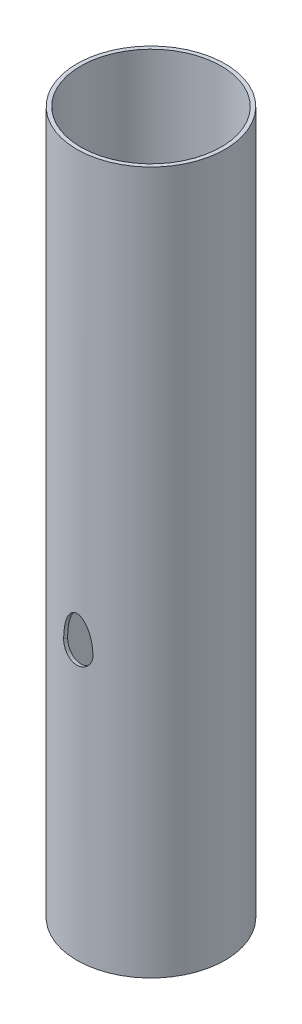
SolidWorks part; units mm, degrees
ref_plane "Front Plane" through (0, 0, 0) normal (0, 0, 1) x (1, 0, 0)
ref_plane "Top Plane" through (0, 0, 0) normal (0, 1, 0) x (1, 0, 0)
ref_plane "Right Plane" through (0, 0, 0) normal (1, 0, 0) x (0, 0, -1)
sketch "Sketch2" plane through (0, 0, 0) normal (0, 1, 0) x (1, 0, 0)
  circle A0 centre (0, 0) radius 36
  circle A1 centre (0, 0) radius 38
  dimension "D1" = 2
  dimension "D2" = 76
extrude "Boss-Extrude1" add sketch "Sketch2" along normal blind 360
ref_axis "Axis1" through (41.8, 0, 0) along (-1, 0, 0)
ref_plane "Plane1" through (0, 0, 0) normal (0, 0.2045, 0.9789) x (-1, 0, 0)
sketch "Sketch3" plane through (0, 0, 0) normal (0, 0.2045, 0.9789) x (-1, 0, 0)
  line L0 (0, 41.8) -> (0, -41.8) construction
  line L2 (-41.8, 0) -> (41.8, 0) construction
  arc A0 (7.5, -128) -> (-7.5, -128) centre (0, -128) ccw
  arc A1 (-7.5, -128) -> (7.5, -128) centre (0, -128) ccw construction
  ellipse E0 centre (0, -128) end of major axis (0, -143) minor radius 7.5 (-7.5, -128) -> (7.5, -128) ccw
  dimension "D1" = 15
  dimension "D2" = 128
  dimension "D3" = 15
extrude "Cut-Extrude1" cut sketch "Sketch3" along normal up to next
